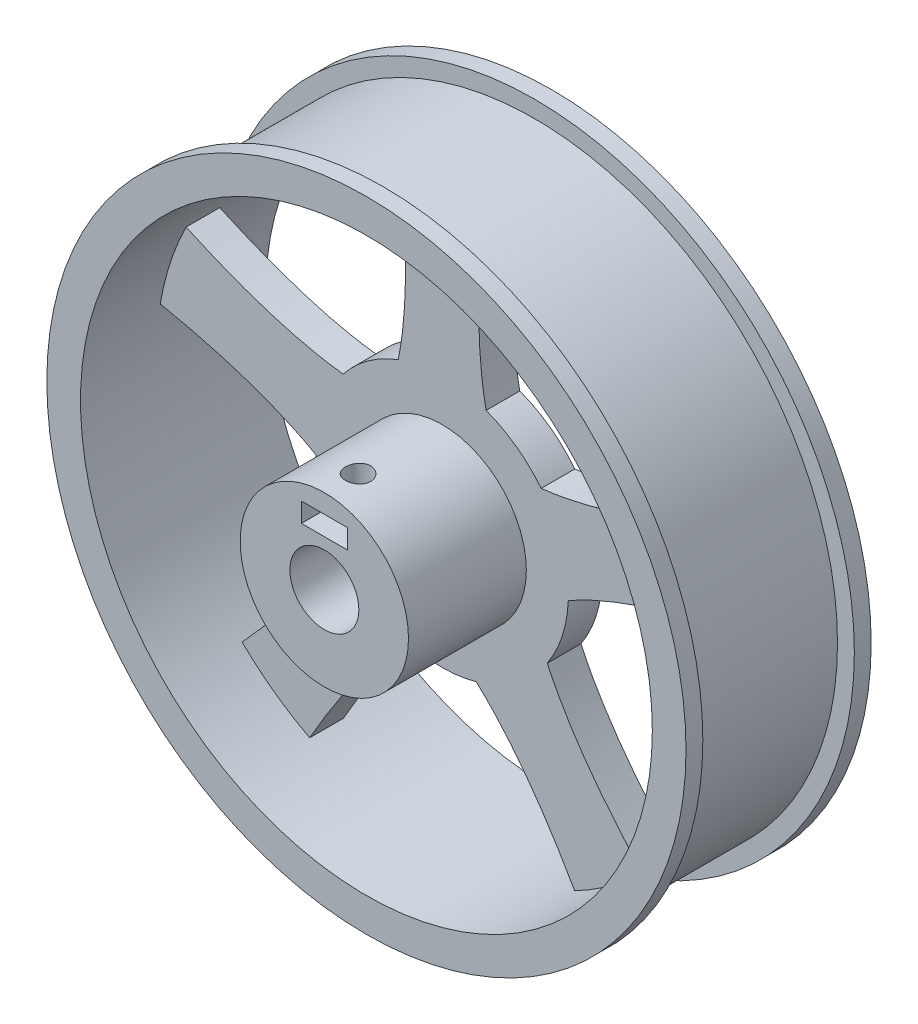
SolidWorks part; units mm, degrees
ref_plane "Front Plane" through (0, 0, 0) normal (0, 0, 1) x (1, 0, 0)
ref_plane "Top Plane" through (0, 0, 0) normal (0, 1, 0) x (1, 0, 0)
ref_plane "Right Plane" through (0, 0, 0) normal (1, 0, 0) x (0, 0, -1)
sketch "Sketch2" plane through (0, 0, 0) normal (1, 0, 0) x (0, 0, -1)
  line L0 (0, 0) -> (0, 35.9709) construction
  line L1 (-9, 35.9709) -> (9, 35.9709)
  line L2 (9, 35.9709) -> (9, 37.9709)
  line L3 (-9, 35.9709) -> (-9, 37.9709)
  line L4 (9, 37.9709) -> (11, 37.9709)
  line L5 (-9, 37.9709) -> (-11, 37.9709)
  line L6 (11, 37.9709) -> (11, 33.9709)
  line L7 (-11, 37.9709) -> (-11, 33.9709)
  line L8 (11, 33.9709) -> (-11, 33.9709)
  line L9 (-10, 0) -> (10, 0)
  point P11 (0, 33.9709)
  point P15 (0, 0)
  dimension "D1" = 18
  dimension "D2" = 2
  dimension "D3" = 2
  dimension "D4" = 4
revolve "Revolve1" add sketch "Sketch2" angle 360 about L9
sketch "Sketch3" plane through (0, 0, 0) normal (0, 0, 1) x (1, 0, 0)
  circle A0 centre (0, 0) radius 15
  circle A1 centre (0, 0) radius 4
  dimension "D1" = 30
  dimension "D2" = 8
extrude "Boss-Extrude1" add sketch "Sketch3" along normal blind 2 and the other way blind 2 separate body contours A0
sketch "Sketch7" plane through (0, 0, 0) normal (0, 0, 1) x (1, 0, 0)
  circle A0 centre (0, 0) radius 4.1
  dimension "D1" = 8.2
sketch "Sketch11" plane through (0, 0, 0) normal (0, 0, 1) x (1, 0, 0)
  line L0 (0, 14.9571) -> (0, 15) construction
  line L1 (0, 33.9709) -> (5, 33.9709)
  line L2 (0, 33.9709) -> (-5, 33.9709)
  line L3 (-5, 33.9709) -> (5, 33.9709)
  line L4 (32.3082, 10.4976) -> (30.7632, 15.2529)
  line L5 (32.3082, 10.4976) -> (33.8533, 5.7423)
  line L6 (19.9676, -27.483) -> (24.0127, -24.5441)
  line L7 (19.9676, -27.483) -> (15.9225, -30.422)
  line L8 (-19.9676, -27.483) -> (-15.9225, -30.422)
  line L9 (-19.9676, -27.483) -> (-24.0127, -24.5441)
  line L10 (-32.3082, 10.4976) -> (-33.8533, 5.7423)
  line L11 (-32.3082, 10.4976) -> (-30.7632, 15.2529)
  circle A0 centre (0, 0) radius 15 construction
  circle A1 centre (0, 0) radius 33.9709 construction
  spline S0 degree 2 poles (5, 33.9709) (3.603, 22.0026) (5.2194, 14.0627) knots 0 0 0 0.277878 0.277878 0.277878
  spline S1 degree 3 poles (5.2194, 14.0627) (2.7127, 14.916) (0.2756, 15.1588) (-2.092, 14.7913) knots 0 0 0 0 0.441009 0.441009 0.441009 0.441009
  spline S2 degree 2 poles (-5, 33.9709) (-3.603, 22.0026) (-5.2194, 14.0627) knots 0 0 0 0.277878 0.277878 0.277878
  spline S3 degree 2 poles (-5.2194, 14.0627) (-2.5171, 14.9241) (0, 14.9571) knots 0 0 0 0.374182 0.374182 0.374182
  spline S4 degree 2 poles (30.7632, 15.2529) (19.8123, 10.2258) (11.7615, 9.3095) knots 0 0 0 0.277878 0.277878 0.277878
  spline S5 degree 2 poles (33.8533, 5.7423) (22.0391, 3.3726) (14.9873, -0.6183) knots 0 0 0 0.277878 0.277878 0.277878
  spline S6 degree 3 poles (14.9873, -0.6183) (15.0242, 2.0294) (14.5021, 4.4223) (13.4209, 6.5604) knots 0 0 0 0 0.441009 0.441009 0.441009 0.441009
  spline S7 degree 2 poles (11.7615, 9.3095) (13.4159, 7.0058) (14.2251, 4.622) knots 0 0 0 0.374182 0.374182 0.374182
  spline S8 degree 2 poles (24.0127, -24.5441) (15.8477, -15.6827) (12.4884, -8.3091) knots 0 0 0 0.277878 0.277878 0.277878
  spline S9 degree 2 poles (15.9225, -30.422) (10.0179, -19.9182) (4.0433, -14.4448) knots 0 0 0 0.277878 0.277878 0.277878
  spline S10 degree 3 poles (4.0433, -14.4448) (6.5728, -13.6618) (8.6872, -12.4257) (10.3866, -10.7367) knots 0 0 0 0 0.441009 0.441009 0.441009 0.441009
  spline S11 degree 2 poles (12.4884, -8.3091) (10.8086, -10.5944) (8.7916, -12.1006) knots 0 0 0 0.374182 0.374182 0.374182
  spline S12 degree 2 poles (-15.9225, -30.422) (-10.0179, -19.9182) (-4.0433, -14.4448) knots 0 0 0 0.277878 0.277878 0.277878
  spline S13 degree 2 poles (-24.0127, -24.5441) (-15.8477, -15.6827) (-12.4884, -8.3091) knots 0 0 0 0.277878 0.277878 0.277878
  spline S14 degree 3 poles (-12.4884, -8.3091) (-10.962, -10.4728) (-9.1331, -12.1018) (-7.0016, -13.196) knots 0 0 0 0 0.441009 0.441009 0.441009 0.441009
  spline S15 degree 2 poles (-4.0433, -14.4448) (-6.7358, -13.5534) (-8.7916, -12.1006) knots 0 0 0 0.374182 0.374182 0.374182
  spline S16 degree 2 poles (-33.8533, 5.7423) (-22.0391, 3.3726) (-14.9873, -0.6183) knots 0 0 0 0.277878 0.277878 0.277878
  spline S17 degree 2 poles (-30.7632, 15.2529) (-19.8123, 10.2258) (-11.7615, 9.3095) knots 0 0 0 0.277878 0.277878 0.277878
  spline S18 degree 3 poles (-11.7615, 9.3095) (-13.3477, 7.1892) (-14.3318, 4.9464) (-14.7138, 2.5811) knots 0 0 0 0 0.441009 0.441009 0.441009 0.441009
  spline S19 degree 2 poles (-14.9873, -0.6183) (-14.9715, 2.2179) (-14.2251, 4.622) knots 0 0 0 0.374182 0.374182 0.374182
  point P49 (0, 0)
  dimension "D1" = 5
  dimension "D2" = 5
  dimension "D3" = 5
extrude "Boss-Extrude3" add sketch "Sketch11" along normal blind 2 and the other way blind 2 contours S16 S19 S18 S17 L11 L10 | S2 S3 S1 S0 L1 L2 | S4 S7 S6 S5 L5 L4 | S8 S11 S10 S9 L7 L6 | S12 S15 S14 S13 L9 L8 region at (-0.0013, 24.3147, 0) region at (23.1242, 7.5149, 0) region at (14.2929, -19.6702, 0) region at (-14.2908, -19.6718, 0) region at (-23.1251, 7.5124, 0)
sketch "Sketch12" plane through (0, 0, 0) normal (0, 0, 1) x (1, 0, 0)
  circle A0 centre (0, 0) radius 10
  dimension "D1" = 20
extrude "Boss-Extrude4" add sketch "Sketch12" along normal blind 16 contours A0
extrude "Cut-Extrude1" cut sketch "Sketch7" against normal through all both and the other way through all
sketch "Sketch13" plane through (0, 0, 16) normal (0, 0, 1) x (1, 0, 0)
  line L0 (0, 0) -> (0, 5.4641) construction
  line L2 (-2.725, 7.7641) -> (2.725, 7.7641)
  line L3 (-2.725, 7.7641) -> (-2.725, 5.4641)
  line L4 (-2.725, 5.4641) -> (2.725, 5.4641)
  line L5 (2.725, 7.7641) -> (2.725, 5.4641)
  point P7 (0, 5.4641)
  dimension "D1" = 2.3
  dimension "D2" = 5.45
extrude "Cut-Extrude2" cut sketch "Sketch13" against normal blind 4
sketch "Sketch14" plane through (0, 5.4641, 0) normal (0, 1, 0) x (1, 0, 0)
  line L0 (-2.725, -12) -> (2.725, -12) construction
  circle A0 centre (0, -12) radius 1.5
  dimension "D1" = 3
extrude "Cut-Extrude3" cut sketch "Sketch14" against normal blind 4 and the other way blind 6
sketch "Sketch16" plane through (0, 5.4641, 0) normal (0, 1, 0) x (1, 0, 0)
  line L1 (0, -15.1246) -> (2.706, -13.5623)
  line L2 (2.706, -13.5623) -> (2.706, -10.4377)
  line L3 (2.706, -10.4377) -> (0, -8.8754)
  line L4 (0, -8.8754) -> (-2.706, -10.4377)
  line L5 (-2.706, -10.4377) -> (-2.706, -13.5623)
  line L6 (-2.706, -13.5623) -> (0, -15.1246)
  circle A0 centre (0, -12) radius 2.706 construction
extrude "Cut-Extrude4" cut sketch "Sketch16" along normal up to surface (2.3 mm away) up to face at (0, 7.7641, 13.5833)
